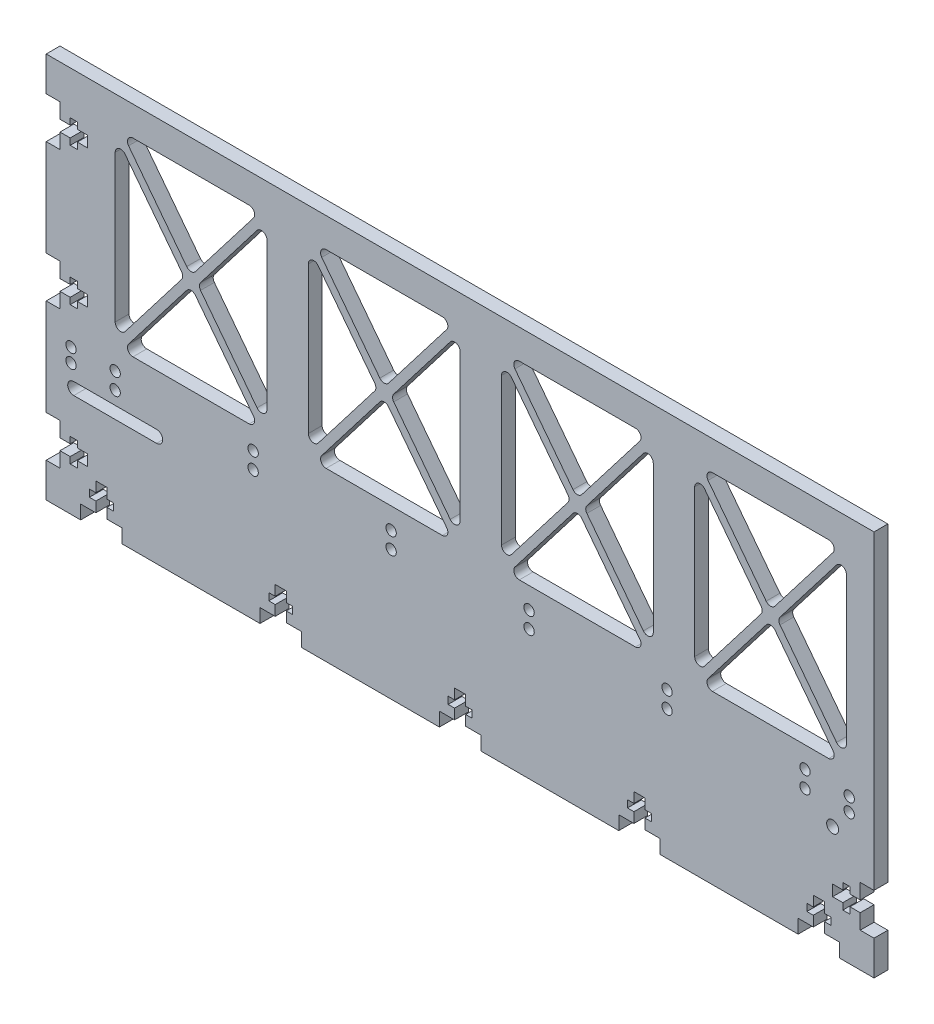
SolidWorks part; units mm, degrees
ref_plane "Front Plane" through (0, 0, 0) normal (0, 0, 1) x (1, 0, 0)
ref_plane "Top Plane" through (0, 0, 0) normal (0, 1, 0) x (1, 0, 0)
ref_plane "Right Plane" through (0, 0, 0) normal (1, 0, 0) x (0, 0, -1)
sketch "Sketch1" plane through (0, 0, 0) normal (0, 0, 1) x (1, 0, 0)
  line L1 (0, 0) -> (381, 0)
  line L2 (0, 0) -> (0, 177.8)
  line L3 (0, 177.8) -> (381, 177.8)
  line L4 (381, 0) -> (381, 177.8)
  dimension "D1" = 381
  dimension "D2" = 177.8
extrude "Boss-Extrude1" add sketch "Sketch1" along normal blind 6.35
sketch "Sketch2" plane through (0, 0, 6.35) normal (0, 0, 1) x (1, 0, 0)
  line L0 (12.7, 50.8) -> (50.8, 50.8) construction
  line L1 (12.7, 53.594) -> (50.8, 53.594)
  line L2 (12.7, 48.006) -> (50.8, 48.006)
  line L3 (0, 0) -> (381, 0) construction
  line L5 (0, 177.8) -> (0, 0) construction
  arc A0 (12.7, 53.594) -> (12.7, 48.006) centre (12.7, 50.8) ccw
  arc A1 (50.8, 48.006) -> (50.8, 53.594) centre (50.8, 50.8) ccw
  point P2 (31.75, 50.8)
  dimension "D2" = 38.1
  dimension "D1" = 5.588
  dimension "D3" = 50.8
  dimension "D4" = 31.75
extrude "Cut-Extrude1" cut sketch "Sketch2" against normal through all
ref_plane "Plane1" through (190.5, 0, 0) normal (-1, 0, 0) x (0, 0, 1)
sketch "Sketch6" plane through (0, 0, 6.35) normal (0, 0, 1) x (1, 0, 0)
  line L2 (15.875, 0) -> (34.925, 0)
  line L3 (15.875, 0) -> (15.875, 6.35)
  line L4 (15.875, 6.35) -> (22.86, 6.35)
  line L5 (34.925, 0) -> (34.925, 6.35)
  line L6 (0, 177.8) -> (0, 0) construction
  line L7 (22.86, 6.35) -> (22.86, 11.049)
  line L8 (22.86, 19.05) -> (27.94, 19.05)
  line L9 (27.94, 6.35) -> (27.94, 11.049)
  line L10 (22.86, 14.351) -> (22.86, 19.05)
  line L11 (19.9009, 14.351) -> (22.86, 14.351)
  line L12 (19.9009, 14.351) -> (19.9009, 11.049)
  line L13 (19.9009, 11.049) -> (22.86, 11.049)
  line L14 (30.8991, 14.351) -> (30.8991, 11.049)
  line L15 (27.94, 14.351) -> (30.8991, 14.351)
  line L16 (27.94, 14.351) -> (27.94, 19.05)
  line L17 (27.94, 11.049) -> (30.8991, 11.049)
  line L18 (27.94, 6.35) -> (34.925, 6.35)
  line L19 (0, 0) -> (381, 0) construction
  point P8 (25.4, 19.05)
  dimension "D1" = 6.35
  dimension "D2" = 19.05
  dimension "D3" = 12.7
  dimension "D4" = 5.08
  dimension "D5" = 25.4
  dimension "D6" = 10.9982
  dimension "D7" = 3.302
  dimension "D10" = 15.875
extrude "Cut-Extrude2" cut sketch "Sketch6" against normal through all
pattern_linear "LPattern1" count 5 spacing 82.55 along (1, 0, 0) of "Cut-Extrude2"
sketch "Sketch8" plane through (0, 0, 6.35) normal (0, 0, 1) x (1, 0, 0)
  line L0 (0, 161.925) -> (0, 142.875)
  line L1 (0, 161.925) -> (6.35, 161.925)
  line L2 (6.35, 161.925) -> (6.35, 154.94)
  line L3 (0, 142.875) -> (6.35, 142.875)
  line L4 (6.35, 154.94) -> (11.049, 154.94)
  line L5 (19.05, 154.94) -> (19.05, 149.86)
  line L6 (6.35, 149.86) -> (11.049, 149.86)
  line L7 (14.351, 154.94) -> (19.05, 154.94)
  line L8 (14.351, 157.8991) -> (14.351, 154.94)
  line L9 (14.351, 157.8991) -> (11.049, 157.8991)
  line L10 (11.049, 157.8991) -> (11.049, 154.94)
  line L11 (14.351, 146.9009) -> (11.049, 146.9009)
  line L12 (14.351, 149.86) -> (14.351, 146.9009)
  line L13 (14.351, 149.86) -> (19.05, 149.86)
  line L14 (11.049, 149.86) -> (11.049, 146.9009)
  line L15 (6.35, 149.86) -> (6.35, 142.875)
  line L16 (0, 177.8) -> (0, 0) construction
  line L17 (381, 177.8) -> (0, 177.8) construction
  point P8 (19.05, 152.4)
  dimension "D1" = 6.35
  dimension "D2" = 5.08
  dimension "D3" = 12.7
  dimension "D4" = 10.9982
  dimension "D5" = 3.302
  dimension "D6" = 15.875
  dimension "D7" = 19.05
extrude "Cut-Extrude4" cut sketch "Sketch8" against normal through all
pattern_linear "LPattern3" count 2 spacing 63.5 along (0, -1, 0) of "Cut-Extrude4"
sketch "Sketch9" plane through (0, 0, 6.35) normal (0, 0, 1) x (1, 0, 0)
  line L0 (0, 34.925) -> (0, 15.875)
  line L1 (0, 34.925) -> (6.35, 34.925)
  line L2 (6.35, 34.925) -> (6.35, 27.94)
  line L3 (0, 15.875) -> (6.35, 15.875)
  line L4 (6.35, 27.94) -> (11.049, 27.94)
  line L5 (19.05, 27.94) -> (19.05, 22.86)
  line L6 (6.35, 22.86) -> (11.049, 22.86)
  line L7 (14.351, 27.94) -> (19.05, 27.94)
  line L8 (14.351, 30.8991) -> (14.351, 27.94)
  line L9 (14.351, 30.8991) -> (11.049, 30.8991)
  line L10 (11.049, 30.8991) -> (11.049, 27.94)
  line L11 (14.351, 19.9009) -> (11.049, 19.9009)
  line L12 (14.351, 22.86) -> (14.351, 19.9009)
  line L13 (14.351, 22.86) -> (19.05, 22.86)
  line L14 (11.049, 22.86) -> (11.049, 19.9009)
  line L15 (6.35, 22.86) -> (6.35, 15.875)
  line L16 (0, 79.375) -> (0, 0) construction
  line L17 (0, 79.375) -> (6.35, 79.375) construction
  point P8 (19.05, 25.4)
  dimension "D1" = 6.35
  dimension "D2" = 5.08
  dimension "D3" = 12.7
  dimension "D4" = 10.9982
  dimension "D5" = 3.302
  dimension "D6" = 19.05
  dimension "D7" = 63.5
extrude "Cut-Extrude5" cut sketch "Sketch9" against normal through all
mirror "Mirror2" about plane through (190.5, 0, 0) normal (-1, 0, 0) of "Cut-Extrude5"
hole_wizard "M5 Clearance Hole1" positions "Sketch11" profile "Sketch10" hole size "M5" standard "ANSI Metric" end condition through all
sketch "Sketch11" plane through (0, 0, 6.35) normal (0, 0, 1) x (1, 0, 0)
  line L2 (381, 34.925) -> (381, 177.8) construction
  line L3 (365.125, 0) -> (381, 0) construction
  point P0 (361.95, 50.8)
  dimension "D1" = 19.05
  dimension "D2" = 50.8
sketch "Sketch10" plane through (361.95, 50.8, 6.35) normal (1, 0, 0) x (0, -1, 0)
  line L0 (0, 0) -> (0, 6.35)
  line L1 (0, 6.35) -> (2.75, 6.35)
  line L2 (2.75, 6.35) -> (2.75, 0)
  line L5 (2.75, 0) -> (0, 0)
  line L11 (0, -6.35) -> (0, 107.95) construction
  dimension "Thru Hole Dia." = 5.5
  dimension "Thru Hole Depth" = 6.35
sketch "Sketch12" plane through (0, 0, 6.35) normal (0, 0, 1) x (1, 0, 0)
  line L0 (31.75, 67.31) -> (31.75, 59.69) construction
  line L1 (0, 63.5) -> (31.75, 63.5) construction
  line L2 (0, 79.375) -> (0, 34.925) construction
  circle A0 centre (31.75, 59.69) radius 2.3812
  circle A1 centre (31.75, 67.31) radius 2.3812
  dimension "D4" = 4.7625
  dimension "D1" = 31.75
  dimension "D2" = 63.5
  dimension "D3" = 7.62
extrude "Cut-Extrude6" cut sketch "Sketch12" against normal through all
pattern_linear "LPattern4" count 6 spacing 63.5 along (1, 0, 0) of "Cut-Extrude6"
sketch "Sketch13" plane through (0, 0, 6.35) normal (0, 0, 1) x (1, 0, 0)
  line L0 (11.43, 60.325) -> (11.43, 66.675) construction
  line L1 (11.43, 63.5) -> (0, 63.5) construction
  line L2 (0, 79.375) -> (0, 34.925) construction
  circle A0 centre (11.43, 66.675) radius 2.3813
  circle A1 centre (11.43, 60.325) radius 2.3813
  dimension "D2" = 4.7625
  dimension "D1" = 6.35
  dimension "D3" = 11.43
  dimension "D4" = 63.5
extrude "Cut-Extrude7" cut sketch "Sketch13" against normal through all
mirror "Mirror3" about plane through (190.5, 0, 0) normal (-1, 0, 0) of "Cut-Extrude7"
sketch "Sketch14" plane through (0, 0, 6.35) normal (0, 0, 1) x (1, 0, 0)
  line L0 (31.75, 161.925) -> (31.75, 79.375)
  line L1 (31.75, 79.375) -> (63.5, 120.65)
  line L2 (63.5, 120.65) -> (31.75, 161.925)
  line L3 (31.75, 120.65) -> (0, 120.65) construction
  line L4 (0, 142.875) -> (0, 98.425) construction
  line L5 (31.75, 120.65) -> (63.5, 120.65) construction
  line L6 (66.675, 177.8) -> (66.675, 0) construction
  line L7 (381, 177.8) -> (0, 177.8) construction
  line L8 (34.925, 0) -> (98.425, 0) construction
  line L9 (101.6, 79.375) -> (69.85, 120.65)
  line L10 (69.85, 120.65) -> (101.6, 161.925)
  line L11 (101.6, 161.925) -> (101.6, 79.375)
  line L12 (63.5, 120.65) -> (69.85, 120.65) construction
  line L13 (34.7699, 164.248) -> (66.675, 122.7714)
  line L14 (66.675, 122.7714) -> (98.5801, 164.248)
  line L15 (98.5801, 164.248) -> (34.7699, 164.248)
  line L16 (31.75, 161.925) -> (34.7699, 164.248) construction
  line L17 (66.675, 118.5286) -> (98.5801, 77.052)
  line L18 (98.5801, 77.052) -> (34.7699, 77.052)
  line L19 (34.7699, 77.052) -> (66.675, 118.5286)
  dimension "D1" = 82.55
  dimension "D2" = 31.75
  dimension "D3" = 31.75
  dimension "D4" = 3.175
  dimension "D5" = 3.81
extrude "Cut-Extrude10" cut sketch "Sketch14" against normal through all
fillet "Fillet1" radius 2.54 12 edges at (63.5, 120.65, 3.175) (31.75, 79.375, 3.175) (31.75, 161.925, 3.175) (34.7699, 164.248, 3.175) (66.675, 122.7714, 3.175) (98.5801, 164.248, 3.175) (101.6, 161.925, 3.175) (69.85, 120.65, 3.175) (101.6, 79.375, 3.175) (98.5801, 77.052, 3.175) (34.7699, 77.052, 3.175) (66.675, 118.5286, 3.175)
pattern_linear "LPattern5" count 4 spacing 88.9 along (1, 0, 0) of "Cut-Extrude10", "Fillet1"
